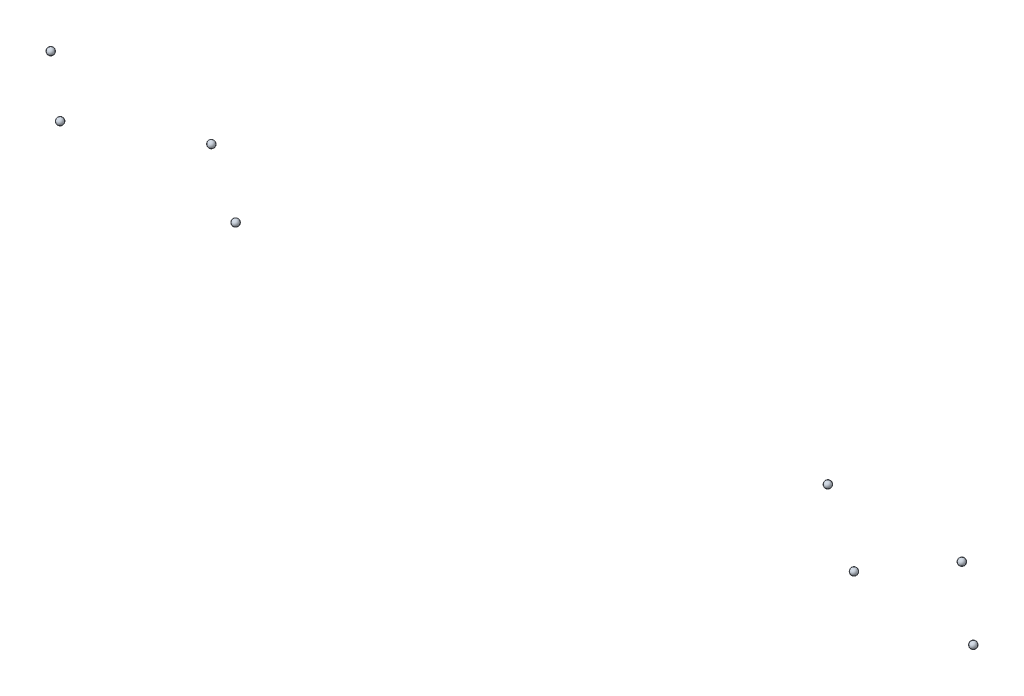
SolidWorks part; units mm, degrees
ref_plane "Front Plane" through (0, 0, 0) normal (0, 0, 1) x (1, 0, 0)
ref_plane "Top Plane" through (0, 0, 0) normal (0, 1, 0) x (1, 0, 0)
ref_plane "Right Plane" through (0, 0, 0) normal (1, 0, 0) x (0, 0, -1)
sketch "Sketch1" plane through (0, 0, 0) normal (0, 1, 0) x (1, 0, 0)
  line L0 (-127, 0) -> (127, 0)
  line L1 (127, 6.35) -> (127, -6.35)
  line L3 (-127, 0) -> (-127, 10.16)
  line L4 (-127, 10.16) -> (-127, 0)
  line L5 (-127, 6.35) -> (-127, -6.35)
  arc A0 (127, -6.35) -> (127, 6.35) centre (127, 0) ccw
  arc A1 (-127, 6.35) -> (-127, -6.35) centre (-127, 0) ccw
  point P2 (0, 0)
  dimension "D2" = 12.7
  dimension "D3" = 10.16
  dimension "D5" = 6.35
  dimension "D1" = 254
  dimension "D4" = 10.16
ref_plane "Plane1" through (127, 0, 0) normal (1, 0, 0) x (0, 0, -1)
sketch "Sketch3" plane through (127, 0, 0) normal (1, 0, 0) x (0, 0, -1)
  line L0 (0, 0) -> (0, -161.925)
  line L1 (0, -161.925) -> (36.322, -161.925)
  dimension "D1" = 161.925
  dimension "D2" = 36.322
ref_plane "Plane2" through (0, 0, -36.322) normal (0, 0, 1) x (1, 0, 0)
sketch "Sketch4" plane through (0, 0, -36.322) normal (0, 0, 1) x (1, 0, 0)
  line L0 (127, -161.925) -> (112.3696, -161.925)
  line L1 (112.3696, -155.575) -> (112.3696, -168.275)
  arc A0 (112.3696, -155.575) -> (112.3696, -168.275) centre (112.3696, -161.925) ccw
  dimension "D2" = 12.7
  dimension "D1" = 14.6304
ref_plane "Plane3" through (-127, 0, 0) normal (1, 0, 0) x (0, 0, -1)
sketch "Sketch5" plane through (-127, 0, 0) normal (1, 0, 0) x (0, 0, -1)
  line L0 (0, 0) -> (0, -152.4)
  line L1 (0, -152.4) -> (34.29, -152.4)
  dimension "D1" = 152.4
  dimension "D2" = 34.29
ref_plane "Plane4" through (0, 0, -34.29) normal (0, 0, 1) x (1, 0, 0)
sketch "Sketch6" plane through (0, 0, -34.29) normal (0, 0, 1) x (1, 0, 0)
  line L0 (-127, -152.4) -> (-111.76, -152.4)
  line L1 (-127, 0) -> (-127, -152.4) construction
  line L2 (-111.76, -158.75) -> (-111.76, -146.05)
  arc A0 (-111.76, -158.75) -> (-111.76, -146.05) centre (-111.76, -152.4) ccw
  dimension "D2" = 12.7
  dimension "D1" = 15.24
revolve "Revolve1" add sketch "Sketch1" angle 360 about L1 region at (129.695, 0, 0)
revolve "Revolve2" add sketch "Sketch1<3>" angle 360 about L5 region at (-129.695, 0, 0)
sketch "Sketch1<3>" plane through (0, 0, 0) normal (0, 1, 0) x (1, 0, 0) same geometry as "Sketch1"
revolve "Revolve3" add sketch "Sketch6" angle 360 about L2 region at (-109.065, -152.4, -34.29)
revolve "Revolve4" add sketch "Sketch4" angle 360 about L1 region at (109.6746, -161.925, -36.322)
sketch "Sketch7" plane through (0, 0, 0) normal (0, 1, 0) x (1, 0, 0)
  line L0 (127, 0) -> (0, -290.9936)
  line L1 (0, -290.9936) -> (-127, 0)
  dimension "D1" = 317.5
  dimension "D2" = 317.5
ref_plane "Plane5" through (0, 0, 290.9936) normal (0, 0, 1) x (1, 0, 0)
sketch "Sketch8" plane through (0, 0, 290.9936) normal (0, 0, 1) x (1, 0, 0)
  line L0 (0, 0) -> (0, -198.12)
  dimension "D1" = 198.12
sketch "Sketch9" plane through (0, 0, 0) normal (0, 1, 0) x (1, 0, 0)
  line L0 (127, 0) -> (-1358.9, 0)
  dimension "D1" = 1485.9
ref_plane "Plane6" through (-1358.9, 0, 0) normal (1, 0, 0) x (0, 0, -1)
sketch "Sketch10" plane through (-1358.9, 0, 0) normal (1, 0, 0) x (0, 0, -1)
  line L0 (0, 0) -> (0, -88.9)
  line L1 (0, -88.9) -> (63.5, -88.9)
  line L2 (63.1553, -82.55) -> (63.1553, -95.25)
  arc A0 (63.1553, -95.25) -> (63.1553, -82.55) centre (63.1553, -88.9) ccw
  dimension "D3" = 12.7
  dimension "D1" = 88.9
  dimension "D2" = 63.5
ref_plane "Plane7" through (0, 0, -63.5) normal (0, 0, 1) x (1, 0, 0)
sketch "Sketch11" plane through (0, 0, -63.5) normal (0, 0, 1) x (1, 0, 0)
  line L0 (-1358.9, -88.9) -> (-1663.7, -88.9)
  line L1 (-1663.7, -88.9) -> (-1663.7, -225.425)
  line L2 (-1358.9, -88.9) -> (-1358.9, -225.425)
  line L3 (-1663.7, -95.25) -> (-1663.7, -82.55)
  arc A0 (-1663.7, -82.55) -> (-1663.7, -95.25) centre (-1663.7, -88.9) ccw
  dimension "D4" = 12.7
  dimension "D1" = 304.8
  dimension "D2" = 136.525
  dimension "D3" = 136.525
ref_plane "Plane8" through (-1663.7, 0, 0) normal (1, 0, 0) x (0, 0, -1)
sketch "Sketch12" plane through (-1663.7, 0, 0) normal (1, 0, 0) x (0, 0, -1)
  line L0 (63.5, -225.425) -> (93.98, -225.425)
  dimension "D1" = 30.48
ref_plane "Plane9" through (0, 0, -93.98) normal (0, 0, 1) x (1, 0, 0)
sketch "Sketch13" plane through (0, 0, -93.98) normal (0, 0, 1) x (1, 0, 0)
  line L0 (-1663.7, -225.425) -> (-1676.4, -225.425)
  line L1 (-1676.4, -219.075) -> (-1676.4, -231.775)
  arc A0 (-1676.4, -219.075) -> (-1676.4, -231.775) centre (-1676.4, -225.425) ccw
  dimension "D2" = 12.7
  dimension "D1" = 12.7
ref_plane "Plane10" through (0, -225.425, 0) normal (0, 1, 0) x (1, 0, 0)
sketch "Sketch14" plane through (0, -225.425, 0) normal (0, 1, 0) x (1, 0, 0)
  line L0 (-1358.9, 63.5) -> (-1358.9, 93.98)
  line L1 (-1358.9, 93.98) -> (-1343.66, 93.98)
  line L2 (-1343.66, 100.33) -> (-1343.66, 87.63)
  arc A0 (-1343.66, 87.63) -> (-1343.66, 100.33) centre (-1343.66, 93.98) ccw
  dimension "D3" = 12.7
  dimension "D1" = 30.48
  dimension "D2" = 15.24
revolve "Revolve5" add sketch "Sketch14" angle 360 about L2 region at (-1340.965, -225.425, -93.98)
revolve "Revolve6" add sketch "Sketch13" angle 360 about L1 region at (-1679.095, -225.425, -93.98)
revolve "Revolve7" add sketch "Sketch10" angle 360 about L2 region at (-1358.9, -88.9, -65.8504)
revolve "Revolve8" add sketch "Sketch11" angle 360 about L3 region at (-1666.395, -88.9, -63.5)
